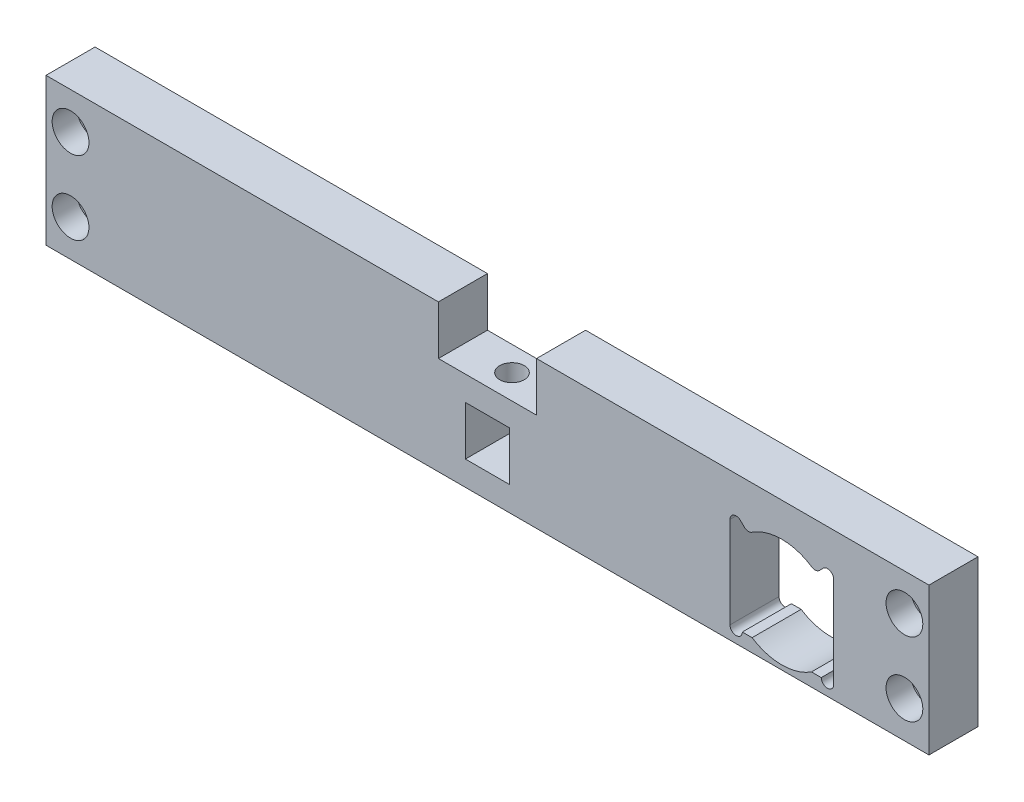
SolidWorks part; units mm, degrees
material "6061-T6 (SS)"
ref_plane "Front Plane" through (0, 0, 0) normal (0, 0, 1) x (1, 0, 0)
ref_plane "Top Plane" through (0, 0, 0) normal (0, 1, 0) x (1, 0, 0)
ref_plane "Right Plane" through (0, 0, 0) normal (1, 0, 0) x (0, 0, -1)
sketch "Sketch1" plane through (0, 0, 0) normal (0, 0, 1) x (1, 0, 0)
  line L1 (-190.5, -19.05) -> (38.1, -19.05)
  line L2 (-190.5, -19.05) -> (-190.5, 19.05)
  line L3 (-190.5, 19.05) -> (38.1, 19.05)
  line L4 (38.1, -19.05) -> (38.1, 19.05)
  line L5 (-190.5, -19.05) -> (38.1, 19.05) construction
  line L6 (-190.5, 19.05) -> (38.1, -19.05) construction
  line L7 (-190.5, 19.05) -> (38.1, 19.05)
  line L8 (-190.5, 19.05) -> (-190.5, -19.05)
  line L11 (-190.5, -19.05) -> (38.1, -19.05)
  line L12 (-190.5, -19.05) -> (-190.5, 19.05)
  line L15 (38.1, -19.05) -> (-190.5, -19.05)
  line L16 (38.1, -19.05) -> (38.1, 19.05)
  line L20 (38.1, -19.05) -> (38.1, 19.05)
  point P0 (0, 0)
  point P14 (-76.2, 0)
  dimension "D1" = 38.1
  dimension "D2" = 228.6
  dimension "D3" = 38.1
extrude "Boss-Extrude1" add sketch "Sketch1" along normal blind 12.7 contours L4 L3 L2 L1 region at (-76.2, 0, 0)
sketch "Sketch5" plane through (0, 0, 12.7) normal (0, 0, 1) x (1, 0, 0)
  line L0 (0, -3.81) -> (11.8187, 8.0087) construction
  line L1 (0, -3.81) -> (11.8187, -3.81) construction
  line L2 (0, -3.81) -> (0, 8.0087) construction
  line L3 (0, 8.0087) -> (11.8187, 8.0087) construction
  line L4 (11.8187, -3.81) -> (11.8187, 8.0087) construction
  line L5 (-10.6872, 9.1402) -> (-8.7721, 7.2252)
  line L6 (0, -3.81) -> (11.8187, -3.81) construction
  line L7 (0, -3.81) -> (0, -15.6287) construction
  line L8 (0, -15.6287) -> (11.8187, -15.6287) construction
  line L9 (11.8187, -3.81) -> (11.8187, -15.6287) construction
  line L10 (0, -3.81) -> (-11.8187, -3.81) construction
  line L11 (0, -3.81) -> (0, -15.6287) construction
  line L12 (0, -15.6287) -> (-11.8187, -15.6287) construction
  line L13 (-11.8187, -3.81) -> (-11.8187, -15.6287) construction
  line L14 (0, -3.81) -> (-11.8187, -3.81) construction
  line L15 (0, -3.81) -> (0, 8.0087) construction
  line L16 (0, 8.0087) -> (-11.8187, 8.0087) construction
  line L17 (-11.8187, -3.81) -> (-11.8187, 8.0087) construction
  line L18 (-13.4189, 8.0087) -> (-13.4189, -15.6287)
  line L19 (13.4189, 8.0087) -> (13.4189, -15.6287)
  line L20 (10.9269, 9.3374) -> (8.7958, 7.2063)
  line L21 (-13.4189, -15.6287) -> (-13.4189, -19.05)
  line L22 (-190.5, -19.05) -> (38.1, -19.05) construction
  line L23 (-13.4189, -19.05) -> (13.4189, -19.05)
  line L24 (13.4189, -19.05) -> (13.4189, -15.6287)
  line L25 (-10.2185, -15.6287) -> (-7.6839, -15.6287)
  line L26 (10.2185, -15.6287) -> (7.6839, -15.6287)
  circle A0 centre (0, -3.81) radius 14.097 construction
  circle A1 centre (11.8187, 8.0087) radius 1.6002
  circle A2 centre (-11.8187, 8.0087) radius 1.6002
  circle A3 centre (-11.8187, -15.6287) radius 1.6002
  circle A4 centre (11.8187, -15.6287) radius 1.6002
  arc A5 (-8.7721, 7.2252) -> (8.7958, 7.2063) centre (0, -3.81) cw
  arc A6 (-7.6839, -15.6287) -> (7.6839, -15.6287) centre (0, -3.81) ccw
  point P6 (9.9681, 6.1581)
  point P7 (10.6872, 6.8772)
  line M8 (-190.5, -19.05) -> (38.1, -19.05)
  dimension "D1" = 28.194
  dimension "D2" = 3.2004
  dimension "D3" = 1.017
  dimension "D4" = 45
  dimension "D5" = 45
  dimension "D6" = 15.24
extrude "Cut-Extrude4" cut sketch "Sketch5" against normal through all contours A5 L5 A2 L18 A3 L21 L24 A4 L19 A1 L20 M8 | A4 | A3 | A2 | A1 L20 region at (-0.0011, -3.8263, 12.7) region at (-11.8187, 8.0087, 12.7) region at (-11.8187, -15.6287, 12.7) region at (11.8205, 8.007, 12.7) region at (11.8187, -15.6287, 12.7)
fillet "Fillet1" radius 1.5875 2 edges at (8.7958, 7.2063, 6.35) (-8.7721, 7.2252, 6.35)
sketch "Sketch6" plane through (0, 0, 12.7) normal (0, 0, 1) x (1, 0, 0)
  line L0 (-190.5, 19.05) -> (38.1, 19.05) construction
  line L1 (-88.9, 19.05) -> (-63.5, 19.05)
  line L2 (-88.9, 19.05) -> (-88.9, 6.35)
  line L3 (-88.9, 6.35) -> (-63.5, 6.35)
  line L4 (-63.5, 19.05) -> (-63.5, 6.35)
  point P6 (-76.2, 6.35)
  point P7 (-76.2, 19.05)
  point P8 (-88.9, 19.05)
  dimension "D1" = 12.7
  dimension "D2" = 25.4
  dimension "D3" = 0
extrude "Cut-Extrude5" cut sketch "Sketch6" against normal through all
sketch "Sketch7" plane through (0, 0, 12.7) normal (0, 0, 1) x (1, 0, 0)
  line L0 (-88.9, 6.35) -> (-63.5, 6.35) construction
  line L1 (-81.915, -12.7) -> (-70.485, -12.7)
  line L2 (-81.915, -12.7) -> (-81.915, 0)
  line L3 (-81.915, 0) -> (-70.485, 0)
  line L4 (-70.485, -12.7) -> (-70.485, 0)
  line L5 (-190.5, -19.05) -> (38.1, -19.05) construction
  point P4 (-76.2, 6.35)
  point P5 (-76.2, 0)
  dimension "D1" = 11.43
  dimension "D2" = 6.35
  dimension "D3" = 6.35
extrude "Cut-Extrude6" cut sketch "Sketch7" against normal through all
sketch "Sketch8" plane through (0, 6.35, 0) normal (0, 1, 0) x (1, 0, 0)
  line L0 (-88.9, 0) -> (-63.5, 0) construction
  line L1 (-88.9, -12.7) -> (-63.5, -12.7) construction
  circle A0 centre (-76.2, -6.35) radius 3.175
  point P2 (-76.2, 0)
  point P3 (-76.2, -12.7)
  dimension "D1" = 6.35
  dimension "D2" = 6.35
extrude "Cut-Extrude7" cut sketch "Sketch8" against normal up to surface (6.35 mm away) up to face at (-76.2, 0, 6.35)
sketch "Sketch9" plane through (0, 0, 0) normal (0, 0, -1) x (-1, 0, 0)
  line L0 (-38.1, -19.05) -> (-38.1, 19.05) construction
  line L1 (-31.75, 9.525) -> (184.15, 9.525) construction
  line L2 (-31.75, 9.525) -> (-31.75, -9.525) construction
  line L3 (-31.75, -9.525) -> (184.15, -9.525) construction
  line L4 (184.15, 9.525) -> (184.15, -9.525) construction
  line L5 (190.5, -19.05) -> (190.5, 19.05) construction
  line L6 (190.5, 19.05) -> (88.9, 19.05) construction
  line L7 (190.5, -19.05) -> (-38.1, -19.05) construction
  circle A0 centre (-31.75, 9.525) radius 3.175
  circle A1 centre (-31.75, -9.525) radius 3.175
  circle A2 centre (184.15, 9.525) radius 3.175
  circle A3 centre (184.15, -9.525) radius 3.175
  dimension "D2" = 6.35
  dimension "D3" = 6.35
  dimension "D1" = 6.35
  dimension "D4" = 9.525
  dimension "D5" = 9.525
extrude "Cut-Extrude8" cut sketch "Sketch9" against normal through all
sketch "Sketch10" plane through (0, 0, 12.7) normal (0, 0, 1) x (1, 0, 0)
  circle A0 centre (-184.15, 9.525) radius 4.7625
  circle A1 centre (-184.15, -9.525) radius 4.7625
  circle A2 centre (31.75, 9.525) radius 4.7625
  circle A3 centre (31.75, -9.525) radius 4.7625
  dimension "D1" = 9.525
extrude "Cut-Extrude9" cut sketch "Sketch10" against normal blind 6.35
